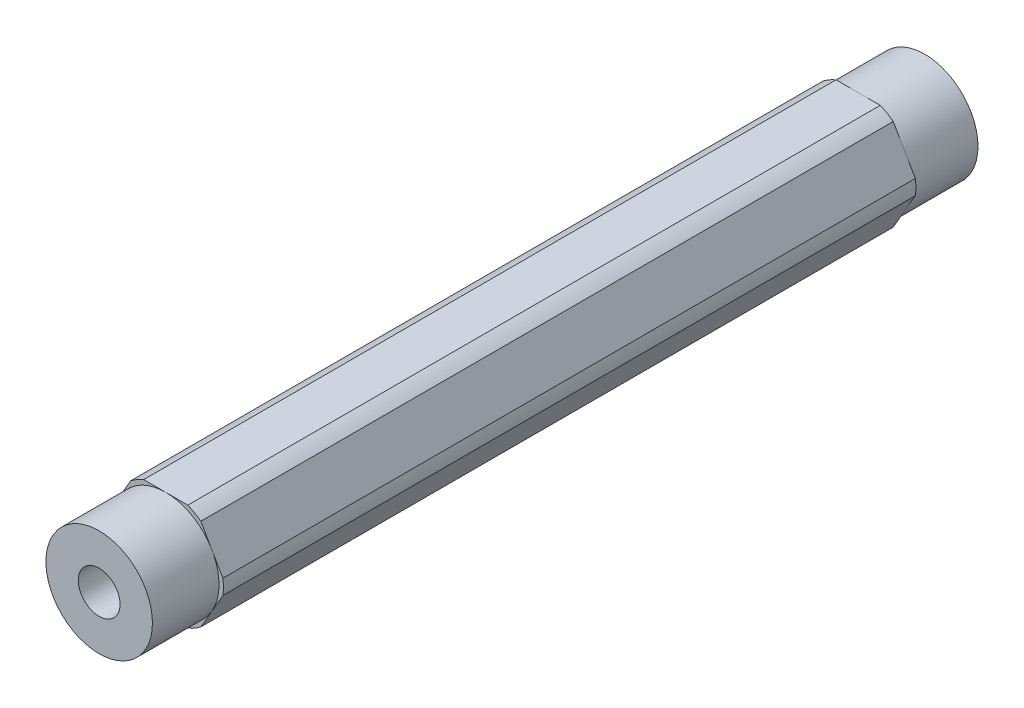
SolidWorks part; units mm, degrees
material "6061-T6 (SS)"
ref_plane "Front Plane" through (0, 0, 0) normal (0, 0, 1) x (1, 0, 0)
ref_plane "Top Plane" through (0, 0, 0) normal (0, 1, 0) x (1, 0, 0)
ref_plane "Right Plane" through (0, 0, 0) normal (1, 0, 0) x (0, 0, -1)
sketch "Sketch1" plane through (0, 0, 0) normal (0, 0, 1) x (1, 0, 0)
  line L1 (3.6662, 6.35) -> (-3.6662, 6.35)
  line L2 (-3.6662, 6.35) -> (-7.3323, 0)
  line L3 (-7.3323, 0) -> (-3.6662, -6.35)
  line L4 (-3.6662, -6.35) -> (3.6662, -6.35)
  line L5 (3.6662, -6.35) -> (7.3323, 0)
  line L6 (7.3323, 0) -> (3.6662, 6.35)
  circle A0 centre (0, 0) radius 6.35 construction
  circle A1 centre (0, 0) radius 2.4892
  circle A2 centre (0, 0) radius 6.875
  point P1 (0, 6.35)
  dimension "D1" = 12.7
  dimension "D2" = 4.9784
  dimension "D3" = 13.75
extrude "Boss-Extrude1" add sketch "Sketch1" along normal mid plane 98.425 contours L6 A2 L1 L2 L3 L4 L5 A1 region at (3.3439, 5.7918, 0)
sketch "Sketch2" plane through (0, 0, 49.2125) normal (0, 0, 1) x (1, 0, 0)
  circle A0 centre (0, 0) radius 6.35
  dimension "D1" = 12.7
extrude "Cut-Extrude1" cut sketch "Sketch2" against normal blind 7.9375 flip side to cut
mirror "Mirror1" about plane through (0, 0, 0) normal (0, 0, 1) of "Cut-Extrude1"
equation "\"D3@Sketch1\"=13.75mm"
